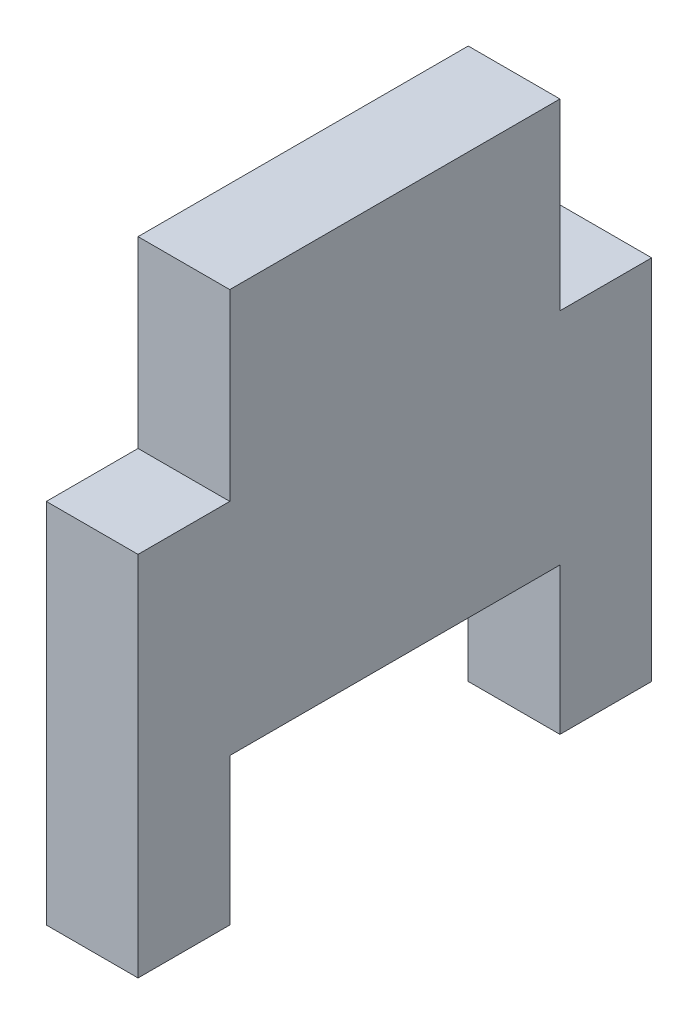
SolidWorks part; units mm, degrees
material "Balsa"
ref_plane "Front Plane" through (0, 0, 0) normal (0, 0, 1) x (1, 0, 0)
ref_plane "Top Plane" through (0, 0, 0) normal (0, 1, 0) x (1, 0, 0)
ref_plane "Right Plane" through (0, 0, 0) normal (1, 0, 0) x (0, 0, -1)
sketch "Sketch1" plane through (0, 0, 0) normal (1, 0, 0) x (0, 0, -1)
  line L0 (0, 0) -> (0, 12.7) construction
  line L1 (11.43, 12.7) -> (-11.43, 12.7)
  line L2 (-11.43, 12.7) -> (-11.43, 0)
  line L3 (-11.43, 0) -> (-17.78, 0)
  line L4 (-17.78, 0) -> (-17.78, -25.4)
  line L7 (11.43, 12.7) -> (11.43, 0)
  line L8 (11.43, 0) -> (17.78, 0)
  line L9 (17.78, 0) -> (17.78, -25.4)
  line L13 (-17.78, -25.4) -> (-11.43, -25.4)
  line L14 (-11.43, -25.4) -> (-11.43, -15.24)
  line L15 (-11.43, -15.24) -> (11.43, -15.24)
  line L16 (11.43, -15.24) -> (11.43, -25.4)
  line L17 (11.43, -25.4) -> (17.78, -25.4)
  point P5 (0, 12.7)
  dimension "D1" = 12.7
  dimension "D2" = 6.35
  dimension "D3" = 6.35
  dimension "D4" = 6.35
  dimension "D7" = 10.16
extrude "Boss-Extrude1" add sketch "Sketch1" along normal blind 6.35
